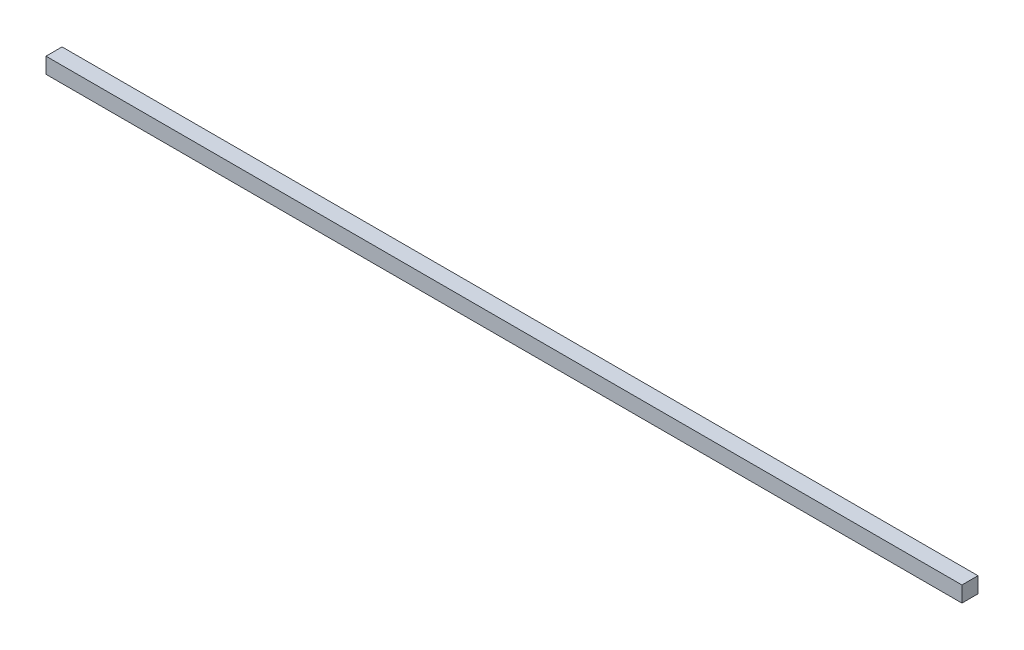
SolidWorks part; units mm, degrees
ref_plane "Спереди" through (0, 0, 0) normal (0, 0, 1) x (1, 0, 0)
ref_plane "Сверху" through (0, 0, 0) normal (0, 1, 0) x (1, 0, 0)
ref_plane "Справа" through (0, 0, 0) normal (1, 0, 0) x (0, 0, -1)
sketch "Эскиз1" plane through (0, 0, 0) normal (0, 0, 1) x (1, 0, 0)
  line L1 (-203.1287, 28.3386) -> (366.6419, 28.3386)
  line L2 (-203.1287, 28.3386) -> (-203.1287, 18.5565)
  line L3 (-203.1287, 18.5565) -> (366.6419, 18.5565)
  line L4 (366.6419, 28.3386) -> (366.6419, 18.5565)
extrude "Бобышка-Вытянуть1" add sketch "Эскиз1" along normal blind 10
